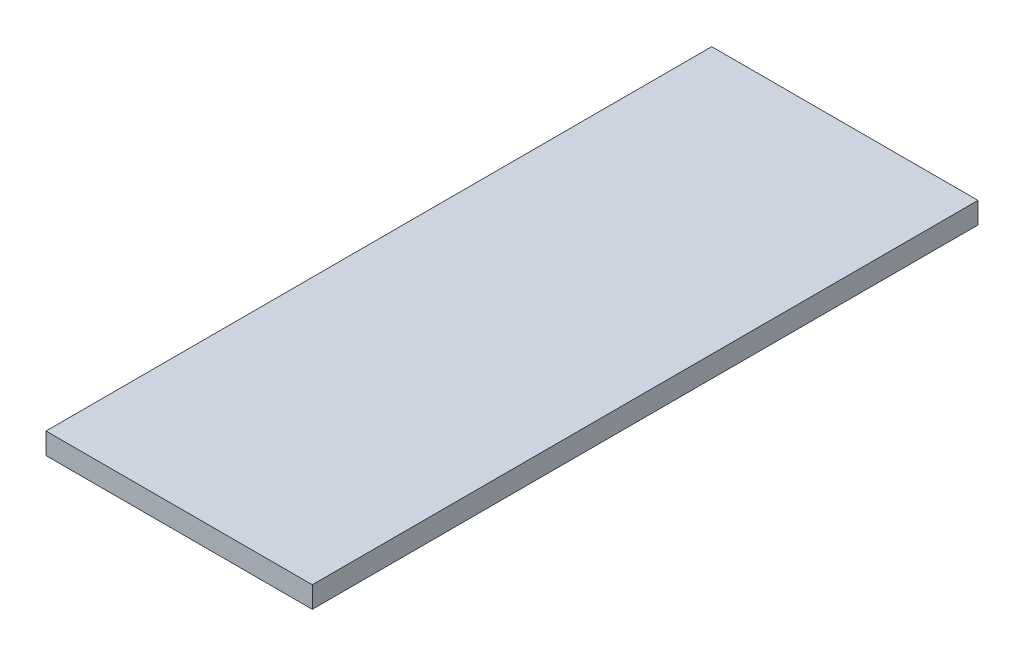
SolidWorks part; units mm, degrees
ref_plane "Front Plane" through (0, 0, 0) normal (0, 0, 1) x (1, 0, 0)
ref_plane "Top Plane" through (0, 0, 0) normal (0, 1, 0) x (1, 0, 0)
ref_plane "Right Plane" through (0, 0, 0) normal (1, 0, 0) x (0, 0, -1)
sketch "Sketch1" plane through (0, 0, 0) normal (0, 1, 0) x (1, 0, 0)
  line L1 (0, 0) -> (20, 0)
  line L2 (0, 0) -> (0, 50)
  line L3 (0, 50) -> (20, 50)
  line L4 (20, 0) -> (20, 50)
  dimension "D1" = 20
  dimension "D2" = 50
extrude "pcb_board" add sketch "Sketch1" along normal blind 1.6
